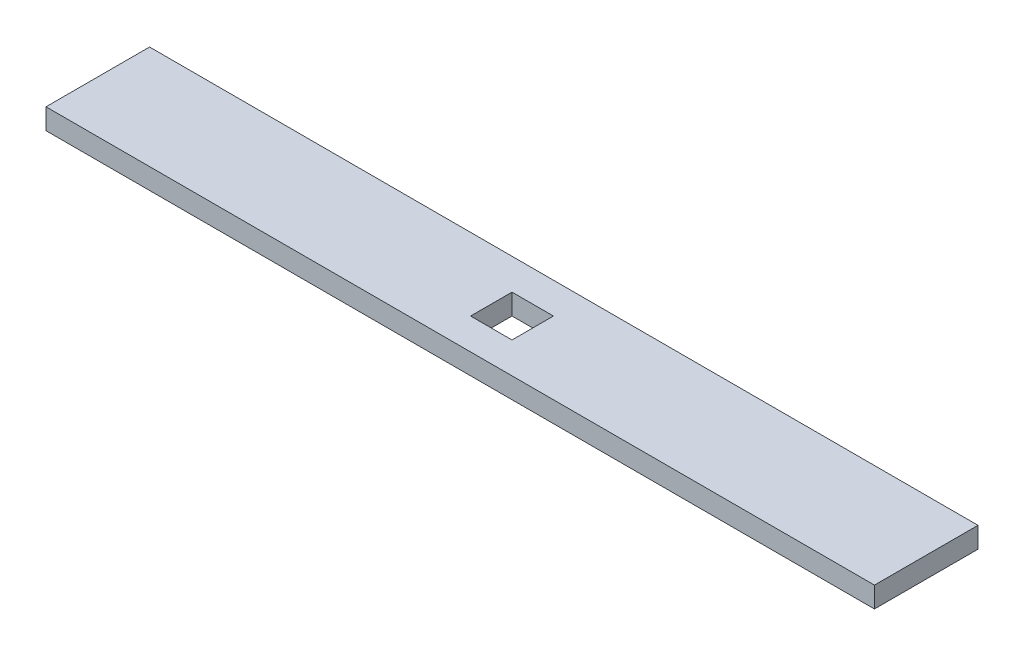
SolidWorks part; units mm, degrees
ref_plane "Front Plane" through (0, 0, 0) normal (0, 0, 1) x (1, 0, 0)
ref_plane "Top Plane" through (0, 0, 0) normal (0, 1, 0) x (1, 0, 0)
ref_plane "Right Plane" through (0, 0, 0) normal (1, 0, 0) x (0, 0, -1)
sketch "Sketch2" plane through (0, 0, 0) normal (0, 1, 0) x (1, 0, 0)
  line L1 (-10, -1.25) -> (10, -1.25)
  line L2 (-10, -1.25) -> (-10, 1.25)
  line L3 (-10, 1.25) -> (10, 1.25)
  line L4 (10, -1.25) -> (10, 1.25)
  line L5 (-10, -1.25) -> (10, 1.25) construction
  line L6 (-10, 1.25) -> (10, -1.25) construction
  point P0 (0, 0)
  dimension "D1" = 2.5
  dimension "D2" = 20
extrude "Boss-Extrude1" add sketch "Sketch2" along normal blind 0.5
sketch "Sketch3" plane through (0, 0.5, 0) normal (0, 1, 0) x (1, 0, 0)
  line L1 (-0.5, -0.5) -> (0.5, -0.5)
  line L2 (-0.5, -0.5) -> (-0.5, 0.5)
  line L3 (-0.5, 0.5) -> (0.5, 0.5)
  line L4 (0.5, -0.5) -> (0.5, 0.5)
  line L5 (-0.5, -0.5) -> (0.5, 0.5) construction
  line L6 (-0.5, 0.5) -> (0.5, -0.5) construction
  circle A0 centre (-13.5, 0) radius 0.5
  circle A1 centre (13.5, 0) radius 0.5
  point P4 (0, 0)
  dimension "D1" = 1
  dimension "D4" = 1
  dimension "D2" = 13.5
  dimension "D3" = 13.5
  dimension "D5" = 1
extrude "Cut-Extrude1" cut sketch "Sketch3" against normal through all both and the other way through all
